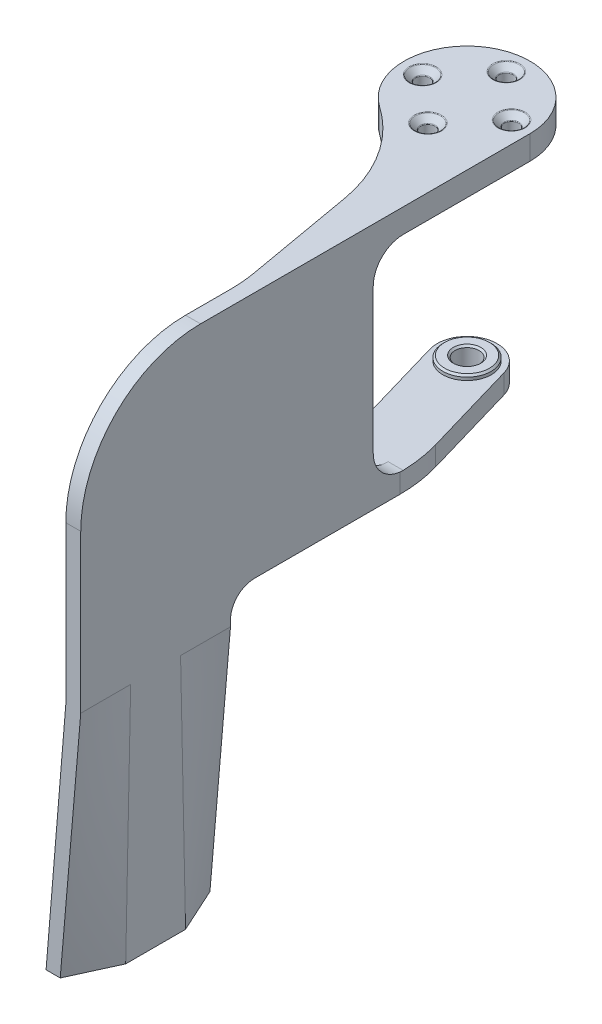
SolidWorks part; units mm, degrees
ref_plane "Front Plane" through (0, 0, 0) normal (0, 0, 1) x (1, 0, 0)
ref_plane "Top Plane" through (0, 0, 0) normal (0, 1, 0) x (1, 0, 0)
ref_plane "Right Plane" through (0, 0, 0) normal (1, 0, 0) x (0, 0, -1)
sketch "Sketch2" plane through (0, 33.6, 0) normal (0, 1, 0) x (1, 0, 0)
  line L0 (14.9082, 11.5925) -> (14.9082, -33.7471)
  line L1 (14.9082, -33.7471) -> (14.9082, -63.4075)
  line L2 (14.9082, -63.4075) -> (12.4082, -63.4075)
  line L3 (12.4082, -63.4075) -> (12.4082, -33.7471)
  line L4 (12.4082, -33.7471) -> (6.2367, 1.2529)
  arc A2 (14.9082, 11.5925) -> (6.2367, 1.2529) centre (4.4082, 11.5925) ccw
  dimension "D2" = 75
  dimension "D3" = 35
  dimension "D4" = 2.5
  dimension "D5" = 10
extrude "Boss-Extrude1" add sketch "Sketch2" along normal blind 4
hole_wizard "CSK for M2 Countersunk Flat Head Screw1" positions "Sketch3" profile "Sketch4" countersink size "M2" standard "ISO"
sketch "Sketch3" plane through (0, 37.6, 0) normal (0, 1, 0) x (1, 0, 0)
  arc A4 (4.0225, 17.7304) -> (3.9158, 19.427) centre (3.9691, 18.5787) ccw construction
  arc A5 (-1.7297, 11.2067) -> (-3.4264, 11.1001) centre (-2.578, 11.1534) ccw construction
  arc A6 (4.9005, 3.7579) -> (4.7939, 5.4546) centre (4.8472, 4.6063) ccw construction
  arc A7 (10.5461, 11.9782) -> (12.2427, 12.0848) centre (11.3944, 12.0315) ccw construction
  point P0 (4.8472, 4.6063)
  point P2 (11.3944, 12.0315)
  point P4 (3.9691, 18.5787)
  point P6 (-2.578, 11.1534)
sketch "Sketch4" plane through (4.8472, 37.6, -4.6063) normal (1, 0, 0) x (0, 0, 1)
  line L0 (0, 0) -> (0, 4.721)
  line L1 (0, 4.721) -> (1.2, 4)
  line L2 (1.2, 4) -> (1.2, 1)
  line L3 (1.2, 1) -> (2.2, 0)
  line L5 (2.2, 0) -> (0, 0)
  line L6 (-1.2, 1) -> (-2.2, 0) construction
  line L10 (0, 4.721) -> (-1.2, 4) construction
  line L11 (0, -6.35) -> (0, 107.95) construction
  dimension "Hole Dia." = 2.4
  dimension "Hole Depth" = 4
  dimension "Near C'Sink Dia." = 4.4
  dimension "Near C'Sink Angle" = 90
  dimension "Drill Angle" = 118
sketch "Sketch5" plane through (0, 33.6, 0) normal (0, -1, 0) x (1, 0, 0)
  line L0 (4.4082, -22.0925) -> (4.4082, -11.5925) construction
  line L1 (-0.0918, -22.0925) -> (-0.0918, -11.5925)
  line L2 (8.9082, -22.0925) -> (8.9082, -11.5925)
  arc A0 (-0.0918, -22.0925) -> (8.9082, -22.0925) centre (4.4082, -22.0925) ccw
  arc A1 (8.9082, -11.5925) -> (-0.0918, -11.5925) centre (4.4082, -11.5925) ccw
  arc A2 (6.2367, -1.2529) -> (14.9082, -11.5925) centre (4.4082, -11.5925) ccw construction
  arc A4 (6.1582, -11.5925) -> (2.6582, -11.5925) centre (4.4082, -11.5925) ccw construction
  arc A8 (8.4003, -11.8433) -> (0.416, -11.3416) centre (4.4082, -11.5925) ccw construction
  point P4 (4.4082, -16.8425)
  dimension "D1" = 0.5
extrude "Cut-Extrude1" cut sketch "Sketch5" against normal blind 1
sketch "Sketch6" plane through (0, 0.5, 0) normal (0, -1, 0) x (1, 0, 0)
  circle A0 centre (4.4082, -11.5925) radius 4.0381
  arc A2 (6.2367, -1.2529) -> (14.9082, -11.5925) centre (4.4082, -11.5925) ccw construction
  arc A3 (2.4082, -15.3856) -> (6.4082, -15.3856) centre (4.4082, -11.5925) ccw construction
  dimension "D1" = 0.25
extrude "Boss-Extrude2" add sketch "Sketch6" along normal blind 0.8 from offset 0.2 separate body
sketch "Sketch7" plane through (0, -0.5, 0) normal (0, -1, 0) x (1, 0, 0)
  line L0 (-0.3923, -10.1941) -> (12.4082, 33.7471)
  line L1 (12.4082, 33.7471) -> (12.4082, 63.4075)
  line L2 (12.4082, 63.4075) -> (14.9082, 63.4075)
  line L3 (14.9082, 63.4075) -> (14.9082, 6.5744)
  line L4 (14.9082, 6.5744) -> (9.2086, -12.9909)
  line L5 (14.9082, 63.4075) -> (14.9082, -11.5925) construction
  arc A0 (-0.3923, -10.1941) -> (9.2086, -12.9909) centre (4.4082, -11.5925) ccw
  dimension "D1" = 5
extrude "Boss-Extrude3" add sketch "Sketch7" along normal blind 3.2
sketch "Sketch10" plane through (0, -3.7, 0) normal (0, -1, 0) x (1, 0, 0)
  circle A0 centre (4.4082, -11.5925) radius 2
  dimension "D1" = 4
extrude "Cut-Extrude2" cut sketch "Sketch10" against normal blind 5
sketch "Sketch11" plane through (0, -3.7, 0) normal (0, -1, 0) x (1, 0, 0)
  circle A0 centre (4.4082, -11.5925) radius 3.75
  arc A1 (-0.3923, -10.1941) -> (9.2086, -12.9909) centre (4.4082, -11.5925) ccw construction
  dimension "D1" = 7.5
extrude "Cut-Extrude3" cut sketch "Sketch11" against normal blind 0.4
sketch "Sketch12" plane through (0, 37.6, 0) normal (0, 1, 0) x (1, 0, 0)
  line L0 (12.4082, -33.7471) -> (12.4082, -63.4075) construction
  line L1 (14.9082, -63.4075) -> (12.4082, -63.4075)
  line L2 (14.9082, -63.4075) -> (14.9082, -38.4075)
  line L3 (14.9082, -38.4075) -> (12.4082, -38.4075)
  line L4 (12.4082, -63.4075) -> (12.4082, -38.4075)
  dimension "D1" = 25
extrude "Boss-Extrude4" add sketch "Sketch12" against normal offset from surface (46.3 mm away) 5 up to face at (4.4082, -3.7, -15.3425) offset beyond the face yes
sketch "Sketch15" plane through (14.9082, 0, 0) normal (1, 0, 0) x (0, 0, -1)
  line L0 (-6.5744, -0.5) -> (-38.4075, -0.5) construction
  line L1 (-38.4075, 33.6) -> (-14.5744, 33.6)
  line L2 (-38.4075, 33.6) -> (-38.4075, -0.5)
  line L3 (-38.4075, -0.5) -> (-14.5744, -0.5)
  line L4 (-14.5744, 33.6) -> (-14.5744, -0.5)
  line L6 (-6.5744, -3.7) -> (-6.5744, -0.5) construction
  point P7 (-6.5744, -0.5)
  point P8 (-9.9967, -0.5)
  dimension "D1" = 8
extrude "Boss-Extrude5" add sketch "Sketch15" against normal up to surface (2.5 mm away) up to face at (12.4082, 11.66, 41.5433)
fillet "Fillet1" radius 5 2 edges at (13.6582, -0.5, 14.5744) (13.6582, 33.6, 14.5744)
fillet "Fillet2" radius 20 1 edges at (13.6582, 37.6, 63.4075)
chamfer "Chamfer1" distance 0.3 angle 45 2 edges at (4.4082, 0.3, -13.5925) (4.4082, 0.3, -15.6306)
fillet "Fillet3" radius 0.2 2 edges at (4.4082, -3.3, -13.5925) (4.4082, -3.3, -15.3425)
chamfer "Chamfer2" distance 0.5 angle 45 3 edges at (4.4082, 34.6, -22.0925) (8.9082, 34.1, -21.0793) (-0.0918, 34.1, -21.0793) first distance on face at (3.9691, 34.6, -19.7787) first distance on face at (8.9082, 34.1, -16.3359) first distance on face at (-0.0918, 34.1, -16.3359)
fillet "Fillet4" radius 0.2 12 edges at (4.8472, 37.6, -2.4063) (11.3944, 37.6, -9.8315) (3.9691, 37.6, -16.3787) (-2.578, 37.6, -8.9534) (11.3944, 36.6, -10.8315) (11.3944, 33.6, -10.8315) (4.8472, 36.6, -3.4063) (4.8472, 33.6, -3.4063) (-2.578, 36.6, -9.9534) (-2.578, 33.6, -9.9534) (3.9691, 34.6, -19.7787) (3.9691, 36.6, -17.3787)
fillet "Fillet6" radius 25 4 edges at (12.4082, 35.6, 33.7471) (6.2367, 35.6, -1.2529) (14.9082, -2.1, 6.5744) (12.4082, -2.1, 33.7471)
fillet "Fillet7" radius 4 1 edges at (13.6582, -3.7, 38.4075)
ref_plane "Plane1" through (0, -48.7, 0) normal (0, 1, 0) x (1, 0, 0)
sketch "Sketch14" plane through (0, -8.7, 0) normal (0, -1, 0) x (1, 0, 0)
  line L0 (22.8976, 55.0742) -> (-9.3679, 55.0742) construction
  line L1 (12.4082, 63.4075) -> (14.9082, 63.4075)
  line L3 (12.4082, 38.4075) -> (14.9082, 38.4075)
  line L5 (22.8976, 46.7409) -> (-9.3679, 46.7409) construction
  line L6 (13.6582, 63.4075) -> (13.6582, 55.0742) construction
  line L7 (13.6582, 55.0742) -> (13.6582, 46.7409) construction
  line L8 (13.6582, 46.7409) -> (13.6582, 38.4075) construction
  line L9 (12.4082, 63.4075) -> (12.4082, 55.0742)
  line L10 (12.4082, 55.0742) -> (12.4082, 46.7409)
  line L11 (12.4082, 46.7409) -> (12.4082, 38.4075)
  line L12 (14.9082, 38.4075) -> (14.9082, 46.7409)
  line L13 (14.9082, 46.7409) -> (14.9082, 55.0742)
  line L14 (14.9082, 55.0742) -> (14.9082, 63.4075)
sketch "Sketch13" plane through (0, -48.7, 0) normal (0, 1, 0) x (1, 0, 0)
  line L0 (9.1165, -38.4075) -> (11.4795, -38.4075) construction
  line L1 (9.1165, -63.4075) -> (11.4795, -63.4075) construction
  line L2 (12.4082, -63.4075) -> (14.9082, -63.4075) construction
  line L5 (14.9082, -38.4075) -> (12.4082, -38.4075) construction
  line L6 (14.9082, -63.4075) -> (14.9082, -38.4075) construction
  line L13 (14.9082, -50.9075) -> (-9.5918, -50.9075) construction
  line L14 (14.9082, -45.9129) -> (14.9082, -55.9022)
  line L15 (14.9082, -55.9022) -> (11.4795, -63.4075)
  line L16 (11.4795, -63.4075) -> (9.1165, -63.4075)
  line L17 (9.1165, -63.4075) -> (12.9082, -55.1075)
  line L18 (12.9082, -55.1075) -> (12.9082, -46.7075)
  line L19 (9.1165, -38.4075) -> (12.9082, -46.7075)
  line L20 (11.4795, -38.4075) -> (9.1165, -38.4075)
  line L21 (14.9082, -45.9129) -> (11.4795, -38.4075)
  arc A0 (9.1165, -63.4075) -> (9.1165, -38.4075) centre (-9.5918, -50.9075) ccw construction
  arc A1 (11.4795, -63.4075) -> (11.4795, -38.4075) centre (-9.5918, -50.9075) ccw construction
  point P17 (12.9082, -50.9075)
  dimension "D1" = 2
  dimension "D2" = 45
  dimension "D3" = 4.2
loft "Loft1" add profiles "Sketch14", "Sketch13" connector at (12.4082, -8.7, 63.4075) connector at (9.1165, -48.7, 63.4075)
